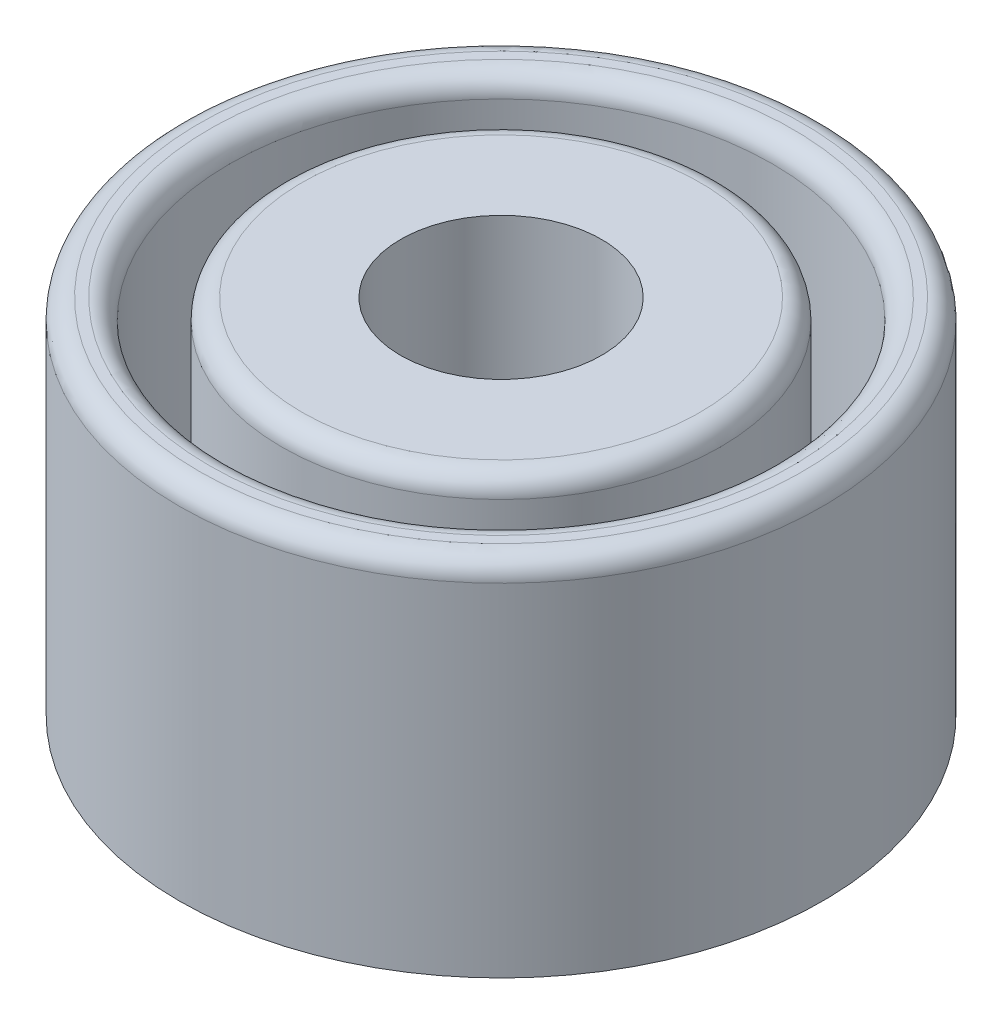
SolidWorks part; units mm, degrees
ref_plane "前基準面" through (0, 0, 0) normal (0, 0, 1) x (1, 0, 0)
ref_plane "上基準面" through (0, 0, 0) normal (0, 1, 0) x (1, 0, 0)
ref_plane "右基準面" through (0, 0, 0) normal (1, 0, 0) x (0, 0, -1)
sketch "草圖1" plane through (0, 0, 0) normal (0, 1, 0) x (1, 0, 0)
  circle A0 centre (0, 0) radius 16
  dimension "D1" = 32
extrude "填料-伸長1" add sketch "草圖1" along normal blind 18
sketch "草圖2" plane through (0, 18, 0) normal (0, 1, 0) x (1, 0, 0)
  circle A0 centre (0, 0) radius 5
  circle A1 centre (0, 0) radius 10.9
  circle A2 centre (0, 0) radius 13.5
  dimension "D1" = 21.8
  dimension "D2" = 27
  dimension "D3" = 10
extrude "除料-伸長1" cut sketch "草圖2" against normal blind 14 contours A0 | A2 A1 region at (0, 18, 0) region at (-13.1182, 18, 0)
sketch "草圖3" plane through (0, 0, 0) normal (0, -1, 0) x (1, 0, 0)
  line L0 (0, -16) -> (0, 16) construction
  line L5 (-16, 0) -> (16, 0) construction
  line L6 (9, -13.2288) -> (9, 13.2288) construction
  circle A0 centre (0, 0) radius 16 construction
  text T0 "<b>NCKU</b>" font "Myanmar Text" height 6
  text T1 "<b>ES</b>" font "Myanmar Text" height 7
  point P8 (0, 0)
  point P11 (9, 0)
  point P12 (0, 0)
  point P13 (0, 0)
  point P15 (0, -14.1452)
  point P16 (0, -16)
  point P17 (9, -13.2288)
  dimension "D1" = 9
extrude "除料-伸長2" cut sketch "草圖3" against normal blind 1
fillet "圓角1" radius 1 3 edges at (0, 18, 16) (0, 18, 13.5) (0, 18, 10.9)
